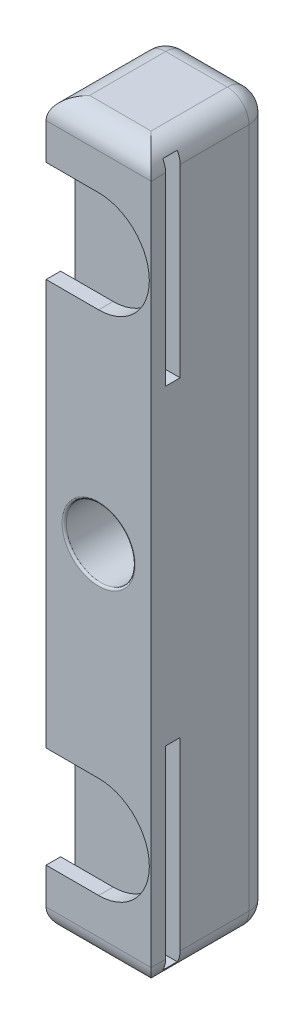
SolidWorks part; units mm, degrees
ref_plane "Front Plane" through (0, 0, 0) normal (1, 0, 0) x (0, 1, 0)
ref_plane "Top Plane" through (0, 0, 0) normal (0, 0, 1) x (0, 1, 0)
ref_plane "Right Plane" through (0, 0, 0) normal (0, 1, 0) x (-1, 0, 0)
sketch "Sketch7" plane through (0, 0, 0) normal (0, 0, 1) x (0, 1, 0)
  line L1 (-50, -7.25) -> (50, -7.25)
  line L2 (-50, -7.25) -> (-50, 7.25)
  line L3 (-50, 7.25) -> (50, 7.25)
  line L4 (50, -7.25) -> (50, 7.25)
  line L5 (-50, -7.25) -> (50, 7.25) construction
  line L6 (-50, 7.25) -> (50, -7.25) construction
  point P0 (0, 0)
  dimension "D1" = 14.5
  dimension "D2" = 100
extrude "Boss-Extrude1" add sketch "Sketch7" along normal blind 16.5
sketch "Sketch8" plane through (0, 0, 16.5) normal (0, 0, 1) x (0, -1, 0)
  circle A0 centre (0, 0) radius 4.75
  dimension "D1" = 9.5
extrude "Cut-Extrude2" cut sketch "Sketch8" against normal blind 16
sketch "Sketch9" plane through (0, 0, 16.5) normal (0, 0, 1) x (1, 0, 0)
  line L0 (0, 0) -> (0, -35) construction
  line L2 (-13.5, -48.5) -> (13.5, -48.5)
  line L3 (-13.5, -48.5) -> (-13.5, -21.5)
  line L4 (-13.5, -21.5) -> (13.5, -21.5)
  line L5 (13.5, -48.5) -> (13.5, -21.5)
  line L6 (-13.5, -48.5) -> (13.5, -21.5) construction
  line L7 (-13.5, -21.5) -> (13.5, -48.5) construction
  dimension "D1" = 35
  dimension "D2" = 27
extrude "Cut-Extrude3" cut sketch "Sketch9" against normal blind 2 from offset 2 offset against normal yes
sketch "Sketch10" plane through (0, 0, 16.5) normal (0, 0, 1) x (1, 0, 0)
  line L0 (0, 0) -> (0, -35) construction
  line L1 (0, -28) -> (-7.25, -28)
  line L2 (-7.25, 50) -> (-7.25, -50) construction
  line L3 (-7.25, -28) -> (-7.25, -42)
  line L4 (0, -42) -> (-7.25, -42)
  arc A0 (0, -42) -> (0, -28) centre (0, -35) ccw
  dimension "D2" = 14
  dimension "D1" = 35
extrude "Cut-Extrude4" cut sketch "Sketch10" against normal blind 2
mirror "Mirror1" about plane through (0, 0, 0) normal (0, 1, 0) of "Cut-Extrude3"
mirror "Mirror2" about plane through (0, 0, 0) normal (0, 1, 0) of "Cut-Extrude4"
fillet "Fillet1" radius 3 1 edges at (-7.25, 0, 0) type face fillet first side face at (-7.25, 0, 13.25) second side face at (0, 0, 0)
fillet "Fillet2" radius 3 1 edges at (7.25, 0, 0) type face fillet first side face at (7.25, 35, 13.5) second side face at (1.5, 0, 0)
fillet "Fillet3" radius 0.3 1 edges at (4.75, 0, 16.5)
fillet "Fillet4" radius 3 12 edges at (-6.3713, -50, 0.8787) (-7.25, -50, 9.75) (0, -50, 16.5) (7.25, -50, 9.75) (6.3713, -50, 0.8787) (0, -50, 0) (0, 50, 16.5) (-7.25, 50, 9.75) (-6.3713, 50, 0.8787) (0, 50, 0) (6.3713, 50, 0.8787) (7.25, 50, 9.75)
